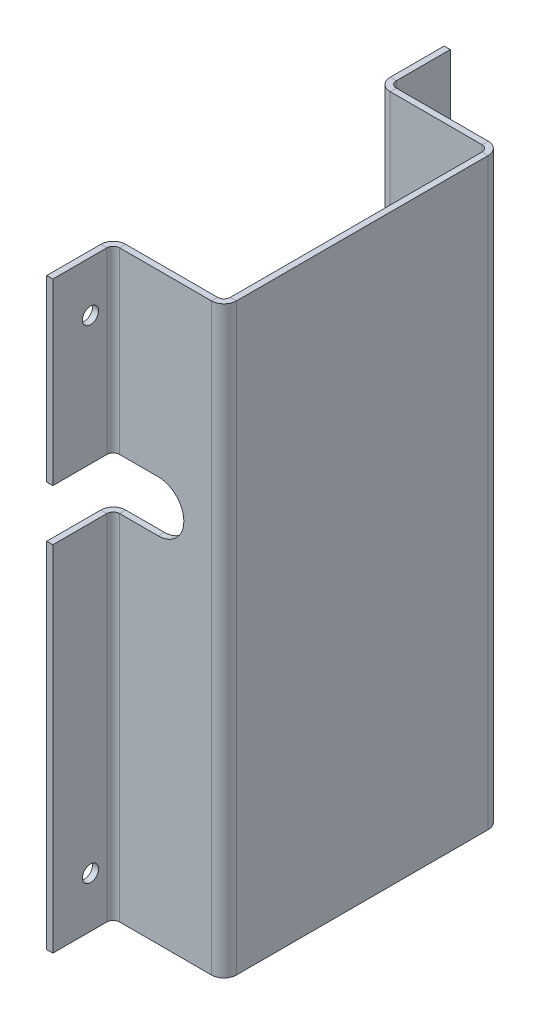
SolidWorks part; units mm, degrees
note: The reader was unsure of these and kept them because the rebuilt part matched: flange length of "Edge-Flange1", "Edge-Flange2".
material "Low Carbon Steel"
ref_plane "Front Plane" through (0, 0, 0) normal (0, 0, 1) x (1, 0, 0)
ref_plane "Top Plane" through (0, 0, 0) normal (0, 1, 0) x (1, 0, 0)
ref_plane "Right Plane" through (0, 0, 0) normal (1, 0, 0) x (0, 0, -1)
sketch "Sketch1" plane through (0, 0, 0) normal (1, 0, 0) x (0, 0, -1)
  line L0 (-62.5, -145) -> (62.5, 145) construction
  line L1 (-62.5, 145) -> (62.5, 145)
  line L2 (-62.5, 145) -> (-62.5, -145)
  line L3 (-62.5, -145) -> (62.5, -145)
  line L4 (62.5, 145) -> (62.5, -145)
  dimension "D1" = 125
  dimension "D2" = 290
base flange "Base-Flange1" sketch "Sketch1" thickness 3.0378 reverse thickness direction no parameters "D1"=3.175
edge flange "Edge-Flange1" sketch "Sketch10" flange profiles "Sketch10", "Sketch11" flange angle 90 flange length 55 flange position bend outside bend radius 3.175 thickness 3.0378 relief rectangular parameters "D6"=10, "D8"=1
sketch "Sketch10" plane through (-3.0378, 0, 62.5) normal (0, 0, 1) x (0, 1, 0)
  line L2 (-145, 0) -> (-145, 55)
  line L3 (-145, 55) -> (145, 55)
  line L4 (145, 55) -> (145, 0)
  line L5 (145, 0) -> (-145, 0) construction
  line L6 (145, 0) -> (-145, 0)
sketch "Sketch11" plane through (-3.0378, 0, -62.5) normal (0, 0, -1) x (0, -1, 0)
  line L1 (145, 0) -> (-145, 0) construction
  line L2 (145, 0) -> (145, 55)
  line L3 (145, 55) -> (-145, 55)
  line L4 (-145, 55) -> (-145, 0)
  line L5 (145, 0) -> (-145, 0)
bend "EdgeBend1" bend radius 3.175 bend angle 90 parameters "D5"=1
bend "EdgeBend2" bend radius 3.175 bend angle 90 parameters "D5"=2
edge flange "Edge-Flange2" sketch "Sketch16" flange profiles "Sketch16", "Sketch17" flange angle 90 flange length 30 flange position material inside bend radius 3.175 thickness 3.0378 relief rectangular parameters "D6"=10, "D8"=1
sketch "Sketch16" plane through (-58.0378, 0, -68.7128) normal (-1, 0, 0) x (0, 1, 0)
  line L2 (-145, 0) -> (-145, 30)
  line L3 (-145, 30) -> (145, 30)
  line L4 (145, 30) -> (145, 0)
  line L5 (-145, 0) -> (145, 0) construction
  line L6 (-145, 0) -> (145, 0)
sketch "Sketch17" plane through (-58.0378, 0, 68.7128) normal (-1, 0, 0) x (0, -1, 0)
  line L0 (-145, 0) -> (145, 0) construction
  line L1 (-145, 0) -> (145, 0)
  line L2 (-145, 0) -> (-145, 30)
  line L3 (-145, 30) -> (145, 30)
  line L4 (145, 30) -> (145, 0)
bend "EdgeBend3" bend radius 3.175 bend angle 90 parameters "D5"=3
bend "EdgeBend4" bend radius 3.175 bend angle 90 parameters "D5"=4
hole_wizard "M6 Clearance Hole1" positions "Sketch19" profile "Sketch18" hole size "M6" standard "Peddi DIN" end condition through all
sketch "Sketch19" plane through (-55, 0, 0) normal (1, 0, 0) x (0, 0, -1)
  line L0 (-80, 120) -> (80, 120) construction
  line L1 (80, 120) -> (80, -120) construction
  line L2 (80, -120) -> (-80, -120) construction
  line L3 (-80, -120) -> (-80, 120) construction
  line L6 (0, 0) -> (0, 120) construction
  line L8 (0, 0) -> (80, 0) construction
  point P0 (-80, 120)
  point P2 (80, 120)
  point P4 (80, -120)
  point P6 (-80, -120)
  dimension "D1" = 160
  dimension "D2" = 240
sketch "Sketch18" plane through (-55, 120, 80) normal (0, 1, 0) x (0, 0, -1)
  line L0 (0, 0) -> (0, 3.0378)
  line L1 (0, 3.0378) -> (4, 3.0378)
  line L2 (4, 3.0378) -> (4, 0)
  line L5 (4, 0) -> (0, 0)
  line L11 (0, -6.35) -> (0, 107.95) construction
  dimension "Thru Hole Dia." = 8
  dimension "Thru Hole Depth" = 3.0378
sketch "Sketch20" plane through (0, 0, 98.7128) normal (0, 0, 1) x (1, 0, 0)
  line L0 (-58.0378, 56.1) -> (-32.6378, 56.1)
  line L1 (-58.0378, -145) -> (-58.0378, 145) construction
  line L2 (-32.6378, 30.7) -> (-58.0378, 30.7)
  line L3 (-58.0378, 30.7) -> (-58.0378, 56.1)
  line L4 (-58.0378, 145) -> (-55, 145) construction
  arc A0 (-32.6378, 56.1) -> (-32.6378, 30.7) centre (-32.6378, 43.4) cw
  point P9 (-56.5189, 145)
  dimension "D1" = 88.9
  dimension "D2" = 25.4
  dimension "D3" = 25.4
extrude "Cut-Extrude1" cut sketch "Sketch20" against normal blind 50 normal cut yes
other "Freeze***"
sketch "Bend-Lines1" plane through (0, 0, 0) normal (0, 1, 0) x (1, 0, 0)
sketch "Bounding-Box1" plane through (0, 0, 0) normal (0, 1, 0) x (1, 0, 0)
sheet metal parameters "Sheet-Metal16" thickness 3.0378 parameters "D1"=3.175
flat pattern "Flat-Pattern16" [suppressed]
sketch "Bend-Lines2" plane through (0, 0, 0) normal (0, 1, 0) x (1, 0, 0)
sketch "Bounding-Box2" [suppressed] plane through (0, 0, 0) normal (0, 1, 0) x (1, 0, 0)
sheet metal parameters "Sheet-Metal17" thickness 3.0378 parameters "D1"=3.175
flat pattern "Flat-Pattern16" [suppressed]
sketch "Bend-Lines2" plane through (0, 0, 0) normal (0, 1, 0) x (1, 0, 0)
sketch "Bounding-Box2" [suppressed] plane through (0, 0, 0) normal (0, 1, 0) x (1, 0, 0)
bend of the flat pattern "Flatten-<EdgeBend1>1"
bend of the flat pattern "Flatten-<EdgeBend2>1"
sheet metal parameters "Sheet-Metal18" thickness 3.0378 parameters "D1"=3.175
flat pattern "Flat-Pattern16" [suppressed]
sketch "Bend-Lines2" plane through (0, 0, 0) normal (0, 1, 0) x (1, 0, 0)
sketch "Bounding-Box2" [suppressed] plane through (0, 0, 0) normal (0, 1, 0) x (1, 0, 0)
bend of the flat pattern "Flatten-<EdgeBend1>1"
bend of the flat pattern "Flatten-<EdgeBend2>1"
bend of the flat pattern "Flatten-<EdgeBend3>1"
bend of the flat pattern "Flatten-<EdgeBend4>1"
sheet metal parameters "Sheet-Metal19" thickness 3.0378 parameters "D1"=3.175
flat pattern "Flat-Pattern16"
sketch "Bend-Lines2" plane through (0, 0, 0) normal (1, 0, 0) x (0, 0, -1)
  line L0 (-118.4562, 145) -> (-118.4562, -145) construction
  line L1 (118.4562, -145) -> (118.4562, 145) construction
  line L2 (65.948, -145) -> (65.948, 145) construction
  line L3 (-65.948, 145) -> (-65.948, -145) construction
  line L4 (-118.4562, 145) -> (-118.4562, -145) construction
  line L5 (118.4562, -145) -> (118.4562, 145) construction
  line L6 (65.948, -145) -> (65.948, 145) construction
  line L7 (-65.948, 145) -> (-65.948, -145) construction
sketch3d "Bounding-Box2" [suppressed]
  line L0 (-148.7292, -145, 0) -> (148.7292, -145, 0) construction
  line L1 (-148.7292, 145, 0) -> (148.7292, 145, 0) construction
  line L2 (-148.7292, -145, 0) -> (-148.7292, 145, 0) construction
  line L3 (148.7292, -145, 0) -> (148.7292, 145, 0) construction
bend of the flat pattern "Flatten-<EdgeBend1>1"
bend of the flat pattern "Flatten-<EdgeBend2>1"
bend of the flat pattern "Flatten-<EdgeBend3>1"
bend of the flat pattern "Flatten-<EdgeBend4>1"
sheet metal parameters "Sheet-Metal20" thickness 3.0378 parameters "D1"=3.175
flat pattern "Flat-Pattern16"
sketch "Bend-Lines2" plane through (0, 0, 0) normal (1, 0, 0) x (0, 0, -1)
  line L0 (-118.4562, 145) -> (-118.4562, -145) construction
  line L1 (118.4562, -145) -> (118.4562, 145) construction
  line L2 (65.948, -145) -> (65.948, 145) construction
  line L3 (-65.948, 145) -> (-65.948, -145) construction
  line L4 (-118.4562, 145) -> (-118.4562, -145) construction
  line L5 (118.4562, -145) -> (118.4562, 145) construction
  line L6 (65.948, -145) -> (65.948, 145) construction
  line L7 (-65.948, 145) -> (-65.948, -145) construction
sketch3d "Bounding-Box2" [suppressed]
  line L0 (-148.7292, -145, 0) -> (148.7292, -145, 0) construction
  line L1 (-148.7292, 145, 0) -> (148.7292, 145, 0) construction
  line L2 (-148.7292, -145, 0) -> (-148.7292, 145, 0) construction
  line L3 (148.7292, -145, 0) -> (148.7292, 145, 0) construction
bend of the flat pattern "Flatten-<EdgeBend1>1"
bend of the flat pattern "Flatten-<EdgeBend2>1"
bend of the flat pattern "Flatten-<EdgeBend3>1"
bend of the flat pattern "Flatten-<EdgeBend4>1"
